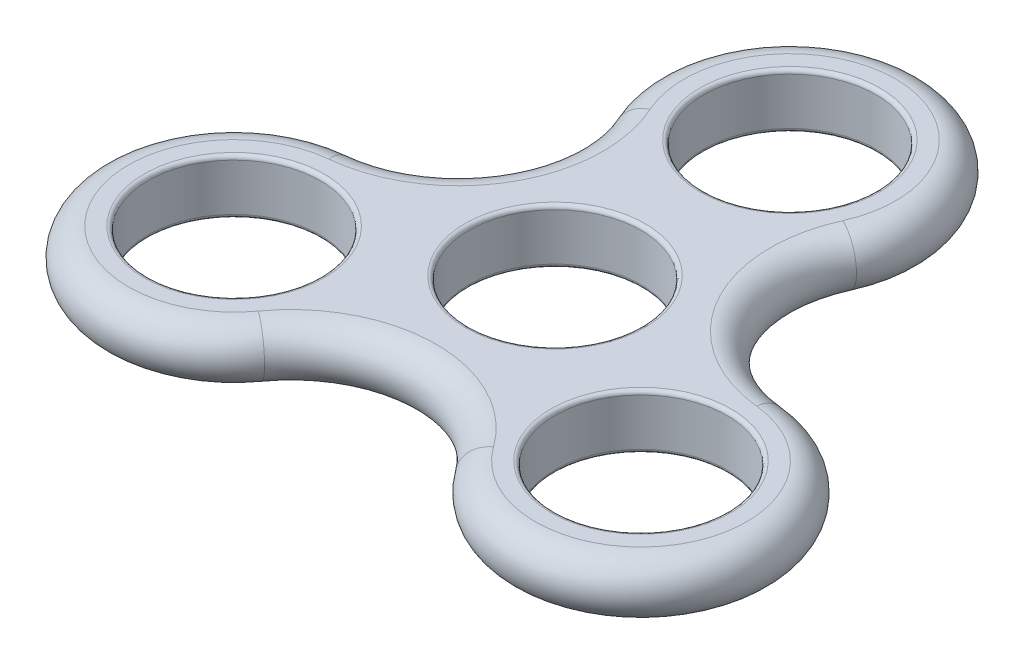
SolidWorks part; units mm, degrees
ref_plane "Front Plane" through (0, 0, 0) normal (0, 0, 1) x (1, 0, 0)
ref_plane "Top Plane" through (0, 0, 0) normal (0, 1, 0) x (1, 0, 0)
ref_plane "Right Plane" through (0, 0, 0) normal (1, 0, 0) x (0, 0, -1)
sketch "Sketch1" plane through (0, 0, 0) normal (0, 1, 0) x (1, 0, 0)
  line L0 (0, 30) -> (0, 0) construction
  circle A0 centre (0, 30) radius 11
  circle A1 centre (0, 0) radius 11
  circle A2 centre (25.9808, -15) radius 11
  circle A3 centre (0, 0) radius 11
  circle A4 centre (-25.9808, -15) radius 11
  circle A5 centre (0, 0) radius 11
  circle A6 centre (0, 30) radius 17
  circle A7 centre (-25.9808, -15) radius 17
  circle A8 centre (25.9808, -15) radius 17
  arc A9 (-15.4961, 23.0092) -> (-27.6746, 1.9154) centre (-29.1691, 16.8408) cw
  arc A10 (-12.1785, -24.9246) -> (12.1785, -24.9246) centre (0, -33.6815) cw
  arc A11 (15.4961, 23.0092) -> (27.6746, 1.9154) centre (29.1691, 16.8408) ccw
  point P14 (0, 0)
  dimension "D2" = 22
  dimension "D5" = 15
  dimension "D6" = 15
  dimension "D7" = 15
  dimension "D1" = 30
  dimension "D4" = 6
  dimension "D3" = 3
extrude "Boss-Extrude1" add sketch "Sketch1" along normal blind 7 contours A0 A6 | A11 A6 A1 A9 A7 A10 A8 | A7 A4 | A8 A2 region at (16.1497, 0, -26.5257) region at (0, 0, -12.2678) region at (-14.8971, 0, 2.7511) region at (38.2297, 0, 3.9164)
fillet "Fillet1" 2 edges at (0, 7, -47) (0, 0, -47) type full round first side face at (0, 7, 0) second side face at (0, 0, 0) middle face at (0, 3.5, -35.0046)
fillet "Fillet2" radius 0.5 8 edges at (25.9808, 0, 26) (25.9808, 7, 26) (0, 0, 11) (0, 7, 11) (-25.9808, 0, 26) (-25.9808, 7, 26) (0, 0, -19) (0, 7, -19)
